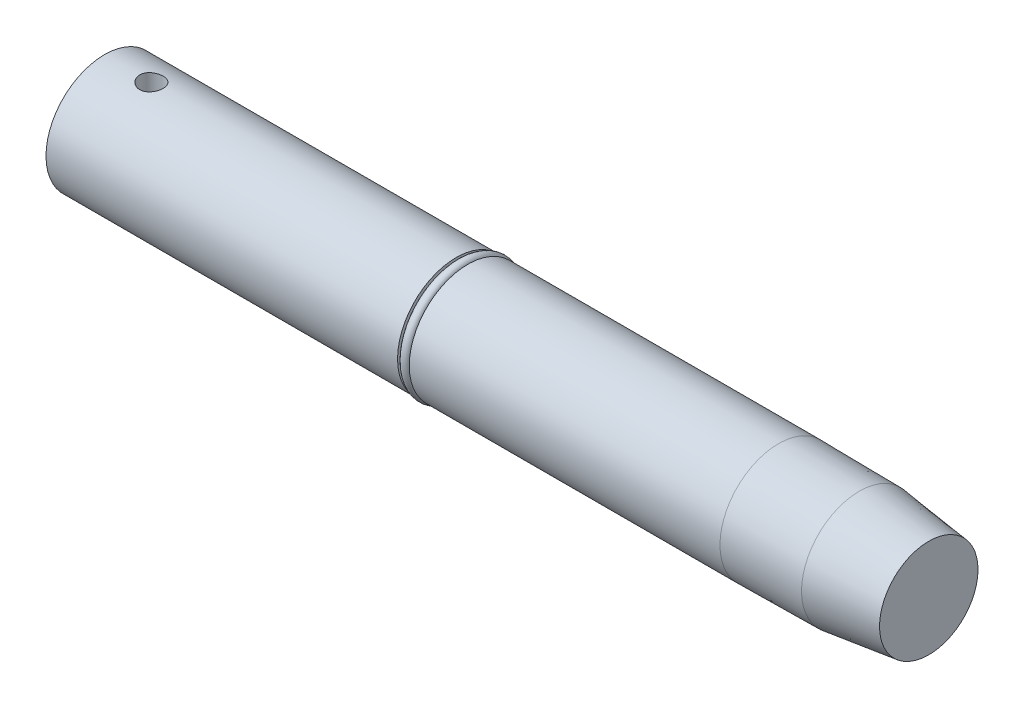
SolidWorks part; units mm, degrees
ref_plane "Front Plane" through (0, 0, 0) normal (0, 0, 1) x (1, 0, 0)
ref_plane "Top Plane" through (0, 0, 0) normal (0, 1, 0) x (1, 0, 0)
ref_plane "Right Plane" through (0, 0, 0) normal (1, 0, 0) x (0, 0, -1)
sketch "Sketch1" plane through (0, 0, 0) normal (1, 0, 0) x (0, 0, -1)
  circle A0 centre (0, 0) radius 15
  dimension "D1" = 30
extrude "Boss-Extrude1" add sketch "Sketch1" along normal blind 211
sketch "Sketch2" plane through (0, 0, 0) normal (0, 1, 0) x (1, 0, 0)
  line L0 (0, 0) -> (116.7157, 0) construction
  line L1 (0, 15) -> (0, -15) construction
  circle A0 centre (12, 0) radius 3
  dimension "D1" = 6
  dimension "D2" = 12
extrude "Cut-Extrude1" cut sketch "Sketch2" against normal blind 199 and the other way blind 199
sketch "Sketch3" plane through (0, 0, 0) normal (0, 0, 1) x (1, 0, 0)
  line L0 (172.5398, 15) -> (211, 14.6)
  line L1 (211, 15) -> (15, 15) construction
  line L2 (211, -15) -> (211, 15) construction
  line L3 (211, 14.6) -> (211, 15)
  line L4 (211, 15) -> (172.5398, 15)
  line L5 (-16.668, 0) -> (255.165, 0) construction
  dimension "D1" = 0.596
  dimension "D2" = 0.4
revolve "Cut-Revolve1" cut sketch "Sketch3" angle 360 about L5
chamfer "Chamfer1" distance 2 angle 83 1 edges at (211, 0, 14.6) first distance on face at (211, 0, 14.6)
sketch "Sketch4" plane through (0, 0, 0) normal (0, 0, 1) x (1, 0, 0)
  line L0 (172.5398, 15) -> (14.9999, 15) construction
  line L1 (93, 15) -> (90, 15)
  line L2 (93, 15) -> (93, 12.9)
  line L3 (93, 12.9) -> (90, 12.9)
  line L4 (90, 15) -> (90, 12.9)
  line L5 (98.8889, 0) -> (114.9051, 0) construction
  line L6 (0, 15) -> (0, -15) construction
  dimension "D1" = 2.1
  dimension "D2" = 3
  dimension "D3" = 90
revolve "Cut-Revolve2" cut sketch "Sketch4" angle 360 about L5
sketch "Sketch5" plane through (0, 0, 0) normal (0, 0, 1) x (1, 0, 0)
  line L0 (65.206, 0) -> (79.9394, 0) construction
  circle A0 centre (91.5251, 14.197) radius 1.2
  point P5 (91.7032, 14.5295)
  point P6 (91.5251, 14.197)
  dimension "D1" = 2.4
revolve "Revolve1" add sketch "Sketch5" angle 360 about L0
equation "\"hatchHoleDiameter\"= 600mm"
equation "\"hullThickness\"= 120mm"
equation "\"gasketHullInterconnectWidth\"= 100mm"
equation "\"collarThickness\"= 20mm"
equation "\"hatchTunnelLength\"=200"
equation "\"oRingDiameter\"=2"
equation "\"boltPatternRadiusInterconnect\"=500"
equation "\"interconnectBoltDiameter\"=30"
equation "\"hatchShaftDiameter\"=20"
equation "\"hatchMinima\"=50"
equation "\"hullDiameter\"=2000"
equation "\"hatchMaxima\"=180"
equation "\"bushingFlatHatch\"=15"
equation "\"hingePivotDiameter\"=20"
equation "\"handleWidth\"=250"
equation "\"handleHeight\"=160"
equation "\"handleThickness\"=25"
equation "\"hatchTopToDogArmCenter\"=33mm"
equation "\"dogArmSize\"=30"
equation "\"hatchPivotHeight\"=40"
equation "\"hatchPivotDistance\"=70"
equation "\"HatchORingDiameter\"=2.1"
equation "\"FrameLength\"= 2600"
equation "\"FrameMidLength\"= 1800"
equation "\"TubeOD\"= 100"
equation "\"FrameBackFlat\"= 500"
equation "\"TubeWall\"=15"
equation "\"TopMemberAngle\"=140"
equation "\"D1@Sketch1\"=\"dogArmSize\""
equation "\"D2@Sketch3\"=\"oRingDiameter\"*0.2"
